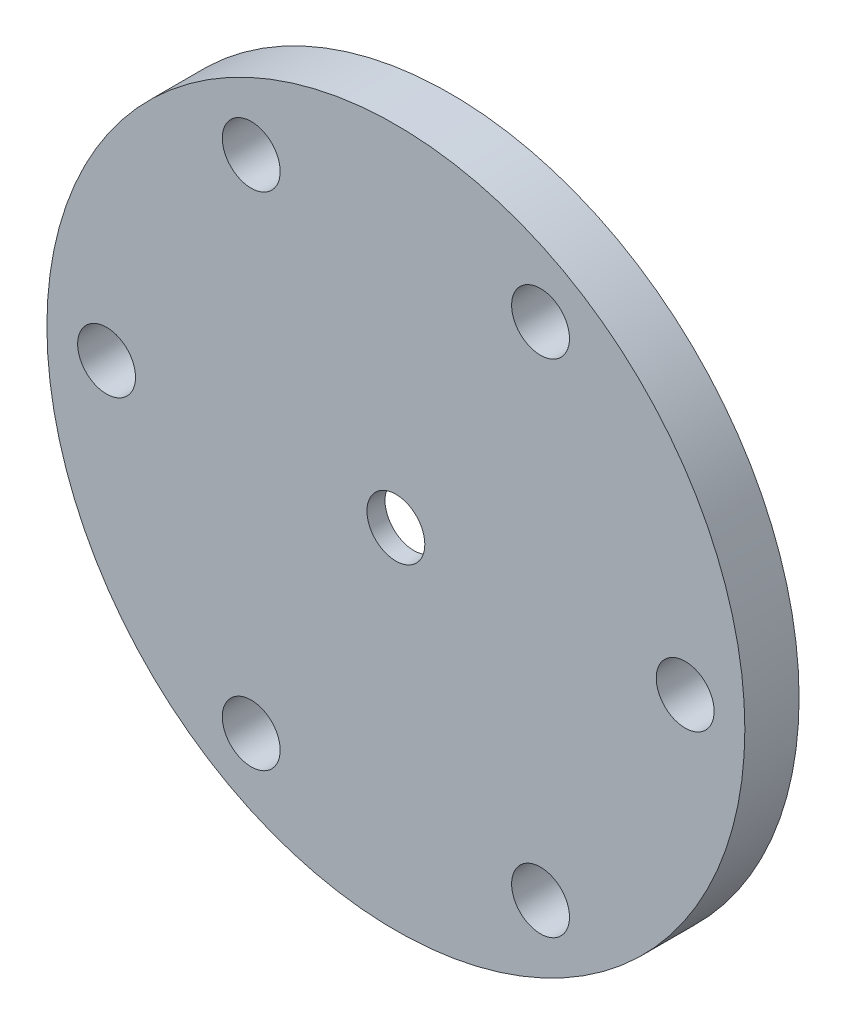
SolidWorks part; units mm, degrees
ref_plane "Front" through (0, 0, 0) normal (0, 0, 1) x (1, 0, 0)
ref_plane "Top" through (0, 0, 0) normal (0, 1, 0) x (1, 0, 0)
ref_plane "Right" through (0, 0, 0) normal (1, 0, 0) x (0, 0, -1)
sketch "Croquis1" plane through (0, 0, 0) normal (0, 0, 1) x (1, 0, 0)
  line L2 (-8, 13.8564) -> (8, -13.8564) construction
  line L3 (0, -55) -> (0, 55) construction
  circle A0 centre (0, 0) radius 19.3
  circle A1 centre (-8, 13.8564) radius 1.6
  circle A2 centre (0, 0) radius 1.6
  circle A3 centre (8, 13.8564) radius 1.6
  circle A4 centre (16, 0) radius 1.6
  circle A5 centre (8, -13.8564) radius 1.6
  circle A6 centre (-8, -13.8564) radius 1.6
  circle A7 centre (-16, 0) radius 1.6
  point P5 (0, 0)
  point P6 (-8.3892, 13.6243)
  dimension "D1" = 38.6
  dimension "D2" = 3.2
  dimension "D3" = 32
  dimension "D5" = 30
  dimension "D4" = 6
extrude "Saliente-Extruir1" add sketch "Croquis1" along normal mid plane 3
sketch "Croquis2" plane through (0, 0, -1.5) normal (0, 0, -1) x (-1, 0, 0)
  circle A0 centre (0, 0) radius 12
  circle A1 centre (0, 0) radius 1.6 construction
  circle A2 centre (0, 0) radius 1.6
  dimension "D1" = 24
extrude "Cortar-Extruir1" cut sketch "Croquis2" against normal blind 2
sketch "Croquis4" plane through (0, 0, 1.5) normal (0, 0, 1) x (1, 0, 0)
  line L0 (0, 7.0522) -> (0, 0) construction
  line L1 (0, -55) -> (0, 55) construction
  line L2 (0, 0) -> (-5.2139, 0) construction
  line L3 (55, 0) -> (-55, 0) construction
